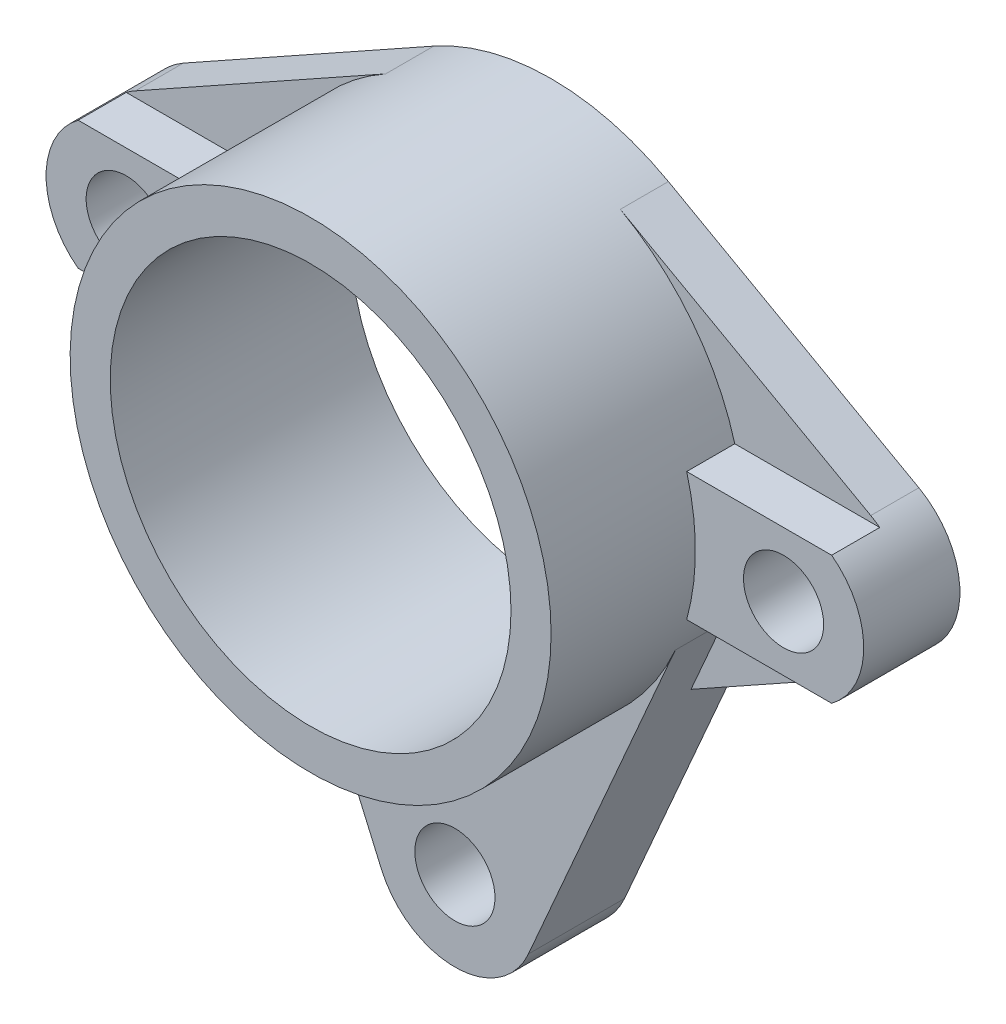
SolidWorks part; units mm, degrees
ref_plane "Front Plane" through (0, 0, 0) normal (0, 0, 1) x (1, 0, 0)
ref_plane "Top Plane" through (0, 0, 0) normal (0, 1, 0) x (1, 0, 0)
ref_plane "Right Plane" through (0, 0, 0) normal (1, 0, 0) x (0, 0, -1)
sketch "Sketch1" plane through (0, 0, 0) normal (0, 0, 1) x (1, 0, 0)
  line L0 (0, 0) -> (0, -35963.0596) construction
  line L1 (0, 0) -> (-35963.0596, 0) construction
  line L2 (45.878, 8.7295) -> (14.6341, 26.1886)
  line L3 (-45.878, 8.7295) -> (-14.6341, 26.1886)
  line L4 (-9.1652, -54) -> (-27.4955, -12)
  line L5 (9.1652, -54) -> (27.4955, -12)
  line L6 (-45.878, -8.7295) -> (-23.454, -21.26)
  line L7 (45.878, -8.7295) -> (23.454, -21.26)
  line L9 (-28.9137, 8) -> (-47, 8)
  line L10 (-28.9137, -8) -> (-47, -8)
  line L12 (28.9137, 8) -> (47, 8)
  line L13 (28.9137, -8) -> (47, -8)
  circle A0 centre (0, 0) radius 25
  circle A1 centre (0, 0) radius 30
  circle A2 centre (41, 0) radius 5
  circle A3 centre (-41, 0) radius 5
  circle A4 centre (0, -50) radius 5
  arc A5 (-45.878, 8.7295) -> (-45.878, -8.7295) centre (-41, 0) ccw
  arc A6 (45.878, -8.7295) -> (45.878, 8.7295) centre (41, 0) ccw
  arc A7 (-9.1652, -54) -> (9.1652, -54) centre (0, -50) ccw
  point P33 (35, 8)
  dimension "D1" = 50
  dimension "D2" = 60
  dimension "D3" = 10
  dimension "D4" = 10
  dimension "D5" = 10
  dimension "D6" = 20
  dimension "D7" = 20
  dimension "D8" = 20
  dimension "D9" = 41
  dimension "D10" = 41
  dimension "D11" = 50
  dimension "D12" = 8
  dimension "D13" = 8
  dimension "D14" = 8
  dimension "D15" = 8
extrude "Boss-Extrude1" add sketch "Sketch1" along normal blind 12 contours L9 A5 L10 A1 A3 | L13 A6 L12 A1 A2 | L4 A7 L5 A1 A4 region at (50.7273, 0, 0) region at (-30.2727, 0, 0) region at (0, -38.8293, 0)
extrude "Boss-Extrude2" add sketch "Sketch1<3>" along normal blind 6 contours L10 A5 L6 L4 A1 | L3 A5 L9 A1 | L12 A6 L2 A1 | L7 A6 L13 A1 L5 region at (32.38, 13.0668, 0) region at (-32.38, 13.0668, 0) region at (33.2706, -12.409, 0) region at (-33.2706, -12.409, 0)
sketch "Sketch1<3>" plane through (0, 0, 0) normal (0, 0, 1) x (1, 0, 0) same geometry as "Sketch1"
extrude "Boss-Extrude3" add sketch "Sketch1<4>" along normal blind 30 contours A1 A0 region at (22.9294, 18.0014, 0)
sketch "Sketch1<4>" plane through (0, 0, 0) normal (0, 0, 1) x (1, 0, 0) same geometry as "Sketch1"
